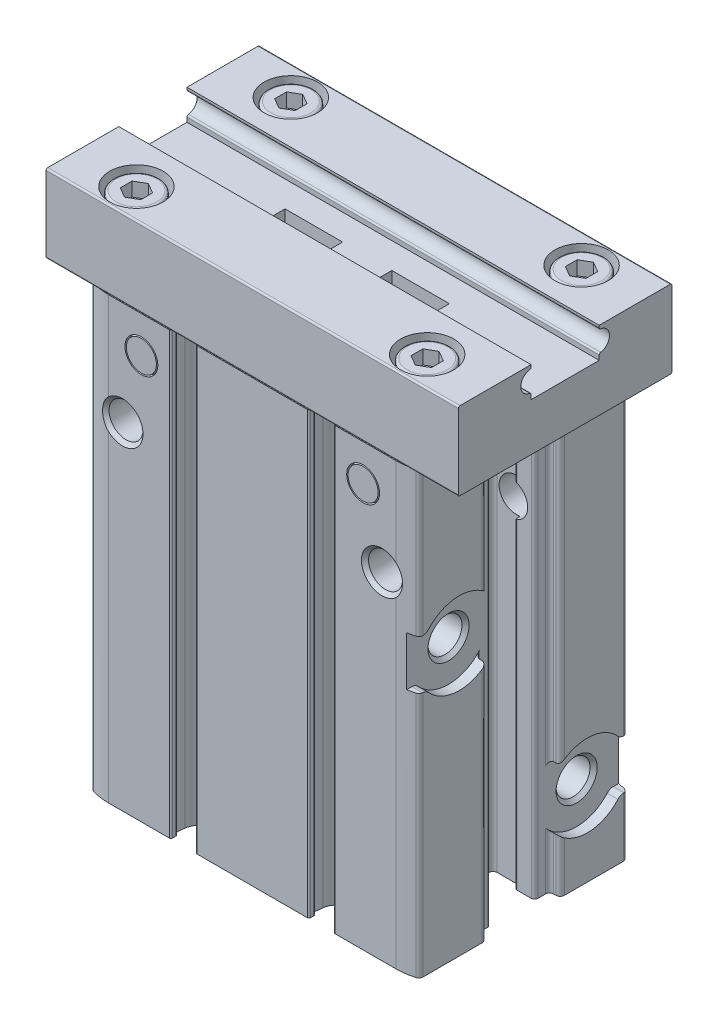
SolidWorks part; units mm, degrees
ref_plane "Front Plane" through (0, 0, 0) normal (0, 0, 1) x (1, 0, 0)
ref_plane "Top Plane" through (0, 0, 0) normal (0, 1, 0) x (1, 0, 0)
ref_plane "Right Plane" through (0, 0, 0) normal (1, 0, 0) x (0, 0, -1)
sketch "Sketch1" plane through (0, 0, 0) normal (0, 1, 0) x (1, 0, 0)
  line L0 (-17.5, -13) -> (17.5, -13)
  line L1 (20, -12.2082) -> (20, 12.2082)
  line L2 (17.5, 13) -> (-17.5, 13)
  line L3 (-20, 12.2082) -> (-20, -12.2082)
  arc A0 (-20, -12.2082) -> (-19.6429, -12.6874) centre (-19.5, -12.2082) ccw
  arc A1 (-19.6429, -12.6874) -> (-17.5, -13) centre (-17.5, -5.5) ccw
  arc A2 (17.5, -13) -> (19.6429, -12.6874) centre (17.5, -5.5) ccw
  arc A3 (19.6429, -12.6874) -> (20, -12.2082) centre (19.5, -12.2082) ccw
  arc A4 (20, 12.2082) -> (19.6429, 12.6874) centre (19.5, 12.2082) ccw
  arc A5 (19.6429, 12.6874) -> (17.5, 13) centre (17.5, 5.5) ccw
  arc A6 (-17.5, 13) -> (-19.6429, 12.6874) centre (-17.5, 5.5) ccw
  arc A7 (-19.6429, 12.6874) -> (-20, 12.2082) centre (-19.5, 12.2082) ccw
extrude "Boss-Extrude1" add sketch "Sketch1" along normal blind 53.6
ref_plane "Plane1" through (0, 41, 0) normal (0, 1, 0) x (1, 0, 0)
sketch "Sketch2" plane through (0, 41, 0) normal (0, 1, 0) x (1, 0, 0)
  line L0 (15.8, -2.6) -> (17.867, -2.6)
  line L1 (17.867, -2.6) -> (17.867, -12.567)
  line L2 (17.867, -12.567) -> (18.3, -13)
  line L3 (18.3, -13) -> (15.8, -13)
  line L4 (15.8, -13) -> (15.8, -2.6)
  line L5 (15.8, -13) -> (15.8, -2.6) construction
revolve "Cut-Revolve1" cut sketch "Sketch2" angle 360 about L5 reverse direction yes
cosmetic thread "Cosmetic Thread1" parameters "D1"=10.4, "D2"=5
sketch "Sketch3" plane through (0, 41, 0) normal (0, 1, 0) x (1, 0, 0)
  line L0 (-15.8, -2.6) -> (-13.733, -2.6)
  line L1 (-13.733, -2.6) -> (-13.733, -12.567)
  line L2 (-13.733, -12.567) -> (-13.3, -13)
  line L3 (-13.3, -13) -> (-15.8, -13)
  line L4 (-15.8, -13) -> (-15.8, -2.6)
  line L5 (-15.8, -13) -> (-15.8, -2.6) construction
revolve "Cut-Revolve2" cut sketch "Sketch3" angle 360 about L5 reverse direction yes
cosmetic thread "Cosmetic Thread2" parameters "D1"=10.4, "D2"=5
hole_wizard "Hole1" positions "Sketch5" profile "Sketch4" legacy
sketch "Sketch5" plane through (0, 0, -13) normal (0, 0, -1) x (-1, 0, 0)
  point P0 (-15.8, 41)
sketch "Sketch4" plane through (15.8, 41, -13) normal (1, 0, 0) x (0, 1, 0)
  line L0 (0, 0) -> (0, 10.4)
  line L1 (0, 10.4) -> (2.067, 10.4)
  line L2 (2.067, 10.4) -> (2.067, 0.433)
  line L3 (2.067, 0.433) -> (2.5, 0)
  line L4 (2.5, 0) -> (0, 0)
  line L5 (0, -6.4453) -> (0, 115.525) construction
  line L6 (-2.067, 0.433) -> (-2.5, 0) construction
  dimension "Diameter" = 4.134
  dimension "Depth" = 10.4
  dimension "C-Sink Angle" = 90
  dimension "C-Sink Diameter" = 5
cosmetic thread "Cosmetic Thread3" parameters "D1"=10.4, "D2"=5
sketch "Sketch6" plane through (0, 41, 0) normal (0, 1, 0) x (1, 0, 0)
  line L0 (-15.8, 13) -> (-13.3, 13)
  line L1 (-13.3, 13) -> (-13.733, 12.567)
  line L2 (-13.733, 12.567) -> (-13.733, 2.6)
  line L3 (-13.733, 2.6) -> (-15.8, 2.6)
  line L4 (-15.8, 2.6) -> (-15.8, 13)
  line L5 (-15.8, 2.6) -> (-15.8, 13) construction
revolve "Cut-Revolve3" cut sketch "Sketch6" angle 360 about L5 reverse direction yes
cosmetic thread "Cosmetic Thread4" parameters "D1"=10.4, "D2"=5
ref_plane "Plane2" through (20, 0, 0) normal (1, 0, 0) x (0, 0, -1)
sketch "Sketch7" plane through (20, 0, 0) normal (1, 0, 0) x (0, 0, -1)
  line L0 (12.2721, 7.2) -> (14, 7.2)
  line L1 (14, 7.2) -> (14, 13.2)
  line L2 (14, 13.2) -> (12.2721, 13.2)
  arc A0 (11.5268, 13.5333) -> (11.5268, 6.8667) centre (7.8, 10.2) ccw
  arc A1 (11.5268, 6.8667) -> (12.2721, 7.2) centre (12.2721, 6.2) cw
  arc A2 (12.2721, 13.2) -> (11.5268, 13.5333) centre (12.2721, 14.2) cw
extrude "Cut-Extrude1" cut sketch "Sketch7" against normal blind 1.3
sketch "Sketch8" plane through (20, 0, 0) normal (1, 0, 0) x (0, 0, -1)
  line L0 (-14, 30) -> (-12.2721, 30)
  line L1 (-12.2721, 36) -> (-14, 36)
  line L2 (-14, 36) -> (-14, 30)
  arc A0 (-12.2721, 30) -> (-11.5268, 29.6667) centre (-12.2721, 29) cw
  arc A1 (-11.5268, 29.6667) -> (-11.5268, 36.3333) centre (-7.8, 33) ccw
  arc A2 (-11.5268, 36.3333) -> (-12.2721, 36) centre (-12.2721, 37) cw
extrude "Cut-Extrude2" cut sketch "Sketch8" against normal blind 1.3
ref_plane "Plane3" through (0, 0, -7.8) normal (0, 0, 1) x (1, 0, 0)
sketch "Sketch9" plane through (0, 0, -7.8) normal (0, 0, 1) x (1, 0, 0)
  line L0 (12.7, 10.2) -> (12.7, 12.267)
  line L1 (12.7, 12.267) -> (18.267, 12.267)
  line L2 (18.267, 12.267) -> (18.7, 12.7)
  line L3 (18.7, 12.7) -> (18.7, 10.2)
  line L4 (18.7, 10.2) -> (12.7, 10.2)
  line L5 (18.7, 10.2) -> (12.7, 10.2) construction
revolve "Cut-Revolve4" cut sketch "Sketch9" angle 360 about L5 reverse direction yes
cosmetic thread "Cosmetic Thread5" parameters "D1"=6, "D2"=5
ref_plane "Plane4" through (0, 0, 7.8) normal (0, 0, 1) x (1, 0, 0)
sketch "Sketch10" plane through (0, 0, 7.8) normal (0, 0, 1) x (1, 0, 0)
  line L0 (12.7, 33) -> (12.7, 35.067)
  line L1 (12.7, 35.067) -> (18.267, 35.067)
  line L2 (18.267, 35.067) -> (18.7, 35.5)
  line L3 (18.7, 35.5) -> (18.7, 33)
  line L4 (18.7, 33) -> (12.7, 33)
  line L5 (18.7, 33) -> (12.7, 33) construction
revolve "Cut-Revolve5" cut sketch "Sketch10" angle 360 about L5 reverse direction yes
cosmetic thread "Cosmetic Thread6" parameters "D1"=6, "D2"=5
ref_plane "Plane5" through (0, 33, 0) normal (0, 1, 0) x (1, 0, 0)
sketch "Sketch11" plane through (0, 33, 0) normal (0, 1, 0) x (1, 0, 0)
  line L0 (-20, 7) -> (-20, 11.2)
  line L1 (-19.8, 11) -> (-18.7, 11)
  line L2 (-18.7, 11) -> (-18.7, 7)
  line L3 (-18.7, 7) -> (-20, 7)
  line L4 (-18.7, 7) -> (-20, 7) construction
  arc A0 (-20, 11.2) -> (-19.8, 11) centre (-19.8, 11.2) ccw
revolve "Cut-Revolve6" cut sketch "Sketch11" angle 360 about L4 reverse direction yes
sketch "Sketch12" plane through (0, 33, 0) normal (0, 1, 0) x (1, 0, 0)
  line L0 (-20, -7) -> (-20, -2.8)
  line L1 (-19.8, -3) -> (-18.7, -3)
  line L2 (-18.7, -3) -> (-18.7, -7)
  line L3 (-18.7, -7) -> (-20, -7)
  line L4 (-18.7, -7) -> (-20, -7) construction
  arc A0 (-20, -2.8) -> (-19.8, -3) centre (-19.8, -2.8) ccw
revolve "Cut-Revolve7" cut sketch "Sketch12" angle 360 about L4 reverse direction yes
sketch "Sketch13" plane through (0, 33, 0) normal (0, 1, 0) x (1, 0, 0)
  line L0 (-18.7, 7) -> (-18.7, 9.5)
  line L1 (-18.7, 9.5) -> (-18.267, 9.067)
  line L2 (-18.267, 9.067) -> (-10.7, 9.067)
  line L3 (-10.7, 9.067) -> (-10.7, 7)
  line L4 (-10.7, 7) -> (-18.7, 7)
  line L5 (-10.7, 7) -> (-18.7, 7) construction
revolve "Cut-Revolve8" cut sketch "Sketch13" angle 360 about L5 reverse direction yes
cosmetic thread "Cosmetic Thread7" parameters "D1"=8, "D2"=5
sketch "Sketch14" plane through (0, 33, 0) normal (0, 1, 0) x (1, 0, 0)
  line L0 (-18.7, -7) -> (-18.7, -4.5)
  line L1 (-18.7, -4.5) -> (-18.267, -4.933)
  line L2 (-18.267, -4.933) -> (-10.7, -4.933)
  line L3 (-10.7, -4.933) -> (-10.7, -7)
  line L4 (-10.7, -7) -> (-18.7, -7)
  line L5 (-10.7, -7) -> (-18.7, -7) construction
revolve "Cut-Revolve9" cut sketch "Sketch14" angle 360 about L5 reverse direction yes
cosmetic thread "Cosmetic Thread8" parameters "D1"=8, "D2"=5
ref_plane "Plane6" through (0, 23, 0) normal (0, 1, 0) x (1, 0, 0)
sketch "Sketch15" plane through (0, 23, 0) normal (0, 1, 0) x (1, 0, 0)
  line L0 (-20, 8) -> (-20, 10.2)
  line L1 (-20, 10.2) -> (-19.8, 10)
  line L2 (-19.8, 10) -> (-16, 10)
  line L3 (-16, 10) -> (-16, 8)
  line L4 (-16, 8) -> (-20, 8)
  line L5 (-16, 8) -> (-20, 8) construction
revolve "Cut-Revolve10" cut sketch "Sketch15" angle 360 about L5 reverse direction yes
sketch "Sketch16" plane through (0, 23, 0) normal (0, 1, 0) x (1, 0, 0)
  line L0 (-20, -8) -> (-20, -5.8)
  line L1 (-20, -5.8) -> (-19.8, -6)
  line L2 (-19.8, -6) -> (-16, -6)
  line L3 (-16, -6) -> (-16, -8)
  line L4 (-16, -8) -> (-20, -8)
  line L5 (-16, -8) -> (-20, -8) construction
revolve "Cut-Revolve11" cut sketch "Sketch16" angle 360 about L5 reverse direction yes
sketch "Sketch17" plane through (0, 0, 0) normal (0, 1, 0) x (1, 0, 0)
  line L0 (-19.5, -4.5) -> (-19.2, -4.5)
  line L1 (-18.7, -4) -> (-18.7, -3.075)
  line L2 (-18.3, -2.675) -> (-16.55, -2.675)
  line L3 (-16.35, -2.875) -> (-16.35, -3.125)
  line L4 (-16.15, -3.325) -> (-13.5, -3.325)
  line L5 (-13, -2.825) -> (-13, 2.825)
  line L6 (-13.5, 3.325) -> (-16.15, 3.325)
  line L7 (-16.35, 3.125) -> (-16.35, 2.875)
  line L8 (-16.55, 2.675) -> (-18.3, 2.675)
  line L9 (-18.7, 3.075) -> (-18.7, 4)
  line L10 (-19.2, 4.5) -> (-19.5, 4.5)
  line L11 (-20, 5) -> (-20, -5)
  arc A0 (-20, -5) -> (-19.5, -4.5) centre (-19.5, -5) cw
  arc A1 (-19.2, -4.5) -> (-18.7, -4) centre (-19.2, -4) ccw
  arc A2 (-18.7, -3.075) -> (-18.3, -2.675) centre (-18.3, -3.075) cw
  arc A3 (-16.55, -2.675) -> (-16.35, -2.875) centre (-16.55, -2.875) cw
  arc A4 (-16.35, -3.125) -> (-16.15, -3.325) centre (-16.15, -3.125) ccw
  arc A5 (-13.5, -3.325) -> (-13, -2.825) centre (-13.5, -2.825) ccw
  arc A6 (-13, 2.825) -> (-13.5, 3.325) centre (-13.5, 2.825) ccw
  arc A7 (-16.15, 3.325) -> (-16.35, 3.125) centre (-16.15, 3.125) ccw
  arc A8 (-16.35, 2.875) -> (-16.55, 2.675) centre (-16.55, 2.875) cw
  arc A9 (-18.3, 2.675) -> (-18.7, 3.075) centre (-18.3, 3.075) cw
  arc A10 (-18.7, 4) -> (-19.2, 4.5) centre (-19.2, 4) ccw
  arc A11 (-19.5, 4.5) -> (-20, 5) centre (-19.5, 5) cw
extrude "Cut-Extrude3" cut sketch "Sketch17" along normal blind 53.6
sketch "Sketch18" plane through (0, 0, 0) normal (0, 1, 0) x (1, 0, 0)
  line L0 (13, 2.825) -> (13, -2.825)
  line L1 (13.5, -3.325) -> (16.15, -3.325)
  line L2 (16.35, -3.125) -> (16.35, -2.875)
  line L3 (16.55, -2.675) -> (18.3, -2.675)
  line L4 (18.7, -3.075) -> (18.7, -4)
  line L5 (19.2, -4.5) -> (19.5, -4.5)
  line L6 (20, -5) -> (20, 5)
  line L7 (19.5, 4.5) -> (19.2, 4.5)
  line L8 (18.7, 4) -> (18.7, 3.075)
  line L9 (18.3, 2.675) -> (16.55, 2.675)
  line L10 (16.35, 2.875) -> (16.35, 3.125)
  line L11 (16.15, 3.325) -> (13.5, 3.325)
  arc A0 (13, -2.825) -> (13.5, -3.325) centre (13.5, -2.825) ccw
  arc A1 (16.15, -3.325) -> (16.35, -3.125) centre (16.15, -3.125) ccw
  arc A2 (16.35, -2.875) -> (16.55, -2.675) centre (16.55, -2.875) cw
  arc A3 (18.3, -2.675) -> (18.7, -3.075) centre (18.3, -3.075) cw
  arc A4 (18.7, -4) -> (19.2, -4.5) centre (19.2, -4) ccw
  arc A5 (19.5, -4.5) -> (20, -5) centre (19.5, -5) cw
  arc A6 (20, 5) -> (19.5, 4.5) centre (19.5, 5) cw
  arc A7 (19.2, 4.5) -> (18.7, 4) centre (19.2, 4) ccw
  arc A8 (18.7, 3.075) -> (18.3, 2.675) centre (18.3, 3.075) cw
  arc A9 (16.55, 2.675) -> (16.35, 2.875) centre (16.55, 2.875) cw
  arc A10 (16.35, 3.125) -> (16.15, 3.325) centre (16.15, 3.125) ccw
  arc A11 (13.5, 3.325) -> (13, 2.825) centre (13.5, 2.825) ccw
extrude "Cut-Extrude4" cut sketch "Sketch18" along normal blind 53.6
sketch "Sketch19" plane through (0, 0, 0) normal (1, 0, 0) x (0, 0, -1)
  line L0 (-13, 62.9) -> (-13, 53.8)
  line L1 (-12.8, 53.6) -> (12.8, 53.6)
  line L2 (13, 53.8) -> (13, 62.9)
  line L3 (12.8, 63.1) -> (4.15, 63.1)
  line L4 (4.15, 63.1) -> (4.15, 62.8361)
  line L5 (4.15, 59.9639) -> (4.15, 59.4)
  line L6 (4.15, 59.4) -> (-4.15, 59.4)
  line L7 (-4.15, 59.4) -> (-4.15, 59.9639)
  line L8 (-4.15, 62.8361) -> (-4.15, 63.1)
  line L9 (-4.15, 63.1) -> (-12.8, 63.1)
  arc A0 (-13, 53.8) -> (-12.8, 53.6) centre (-12.8, 53.8) ccw
  arc A1 (12.8, 53.6) -> (13, 53.8) centre (12.8, 53.8) ccw
  arc A2 (13, 62.9) -> (12.8, 63.1) centre (12.8, 62.9) ccw
  arc A3 (4.15, 62.8361) -> (4.3224, 62.6381) centre (4.35, 62.8361) ccw
  arc A4 (4.3224, 62.6381) -> (4.3224, 60.1619) centre (4.15, 61.4) cw
  arc A5 (4.3224, 60.1619) -> (4.15, 59.9639) centre (4.35, 59.9639) ccw
  arc A6 (-4.15, 59.9639) -> (-4.3224, 60.1619) centre (-4.35, 59.9639) ccw
  arc A7 (-4.3224, 60.1619) -> (-4.3224, 62.6381) centre (-4.15, 61.4) cw
  arc A8 (-4.3224, 62.6381) -> (-4.15, 62.8361) centre (-4.35, 62.8361) ccw
  arc A9 (-12.8, 63.1) -> (-13, 62.9) centre (-12.8, 62.9) ccw
extrude "Boss-Extrude2" add sketch "Sketch19" against normal blind 25.1 and the other way blind 25.1
ref_plane "Plane7" through (0, 0, 8.3) normal (0, 0, 1) x (1, 0, 0)
sketch "Sketch20" plane through (0, 0, 8.3) normal (0, 0, 1) x (1, 0, 0)
  line L0 (15, 10) -> (17.067, 10)
  line L1 (17.067, 10) -> (17.067, 0.433)
  line L2 (17.067, 0.433) -> (17.5, 0)
  line L3 (17.5, 0) -> (15, 0)
  line L4 (15, 0) -> (15, 10)
  line L5 (15, 0) -> (15, 10) construction
revolve "Cut-Revolve12" cut sketch "Sketch20" angle 360 about L5 reverse direction yes
cosmetic thread "Cosmetic Thread9" parameters "D1"=7, "D2"=5
ref_plane "Plane8" through (0, 0, -8.3) normal (0, 0, 1) x (1, 0, 0)
sketch "Sketch21" plane through (0, 0, -8.3) normal (0, 0, 1) x (1, 0, 0)
  line L0 (-15, 10) -> (-12.933, 10)
  line L1 (-12.933, 10) -> (-12.933, 0.433)
  line L2 (-12.933, 0.433) -> (-12.5, 0)
  line L3 (-12.5, 0) -> (-15, 0)
  line L4 (-15, 0) -> (-15, 10)
  line L5 (-15, 0) -> (-15, 10) construction
revolve "Cut-Revolve13" cut sketch "Sketch21" angle 360 about L5 reverse direction yes
cosmetic thread "Cosmetic Thread10" parameters "D1"=7, "D2"=5
ref_plane "Plane9" through (0, 0, 8.3) normal (0, 0, 1) x (1, 0, 0)
ref_plane "Plane10" through (0, 0, -8.3) normal (0, 0, 1) x (1, 0, 0)
ref_plane "Plane11" through (0, 0, 8.5) normal (0, 0, 1) x (1, 0, 0)
sketch "Sketch22" plane through (0, 0, 8.5) normal (0, 0, 1) x (1, 0, 0)
  line L0 (-15.5, 4) -> (-13.5, 4)
  line L1 (-13.5, 4) -> (-13.5, 0.2)
  line L2 (-13.5, 0.2) -> (-13.3, 0)
  line L3 (-13.3, 0) -> (-15.5, 0)
  line L4 (-15.5, 0) -> (-15.5, 4)
  line L5 (-15.5, 0) -> (-15.5, 4) construction
revolve "Cut-Revolve14" cut sketch "Sketch22" angle 360 about L5 reverse direction yes
ref_plane "Plane12" through (0, 0, -8.5) normal (0, 0, 1) x (1, 0, 0)
sketch "Sketch23" plane through (0, 0, -8.5) normal (0, 0, 1) x (1, 0, 0)
  line L0 (15.5, 4) -> (17.5, 4)
  line L1 (17.5, 4) -> (17.5, 0.2)
  line L2 (17.5, 0.2) -> (17.7, 0)
  line L3 (17.7, 0) -> (15.5, 0)
  line L4 (15.5, 0) -> (15.5, 4)
  line L5 (15.5, 0) -> (15.5, 4) construction
revolve "Cut-Revolve15" cut sketch "Sketch23" angle 360 about L5 reverse direction yes
sketch "Sketch24" plane through (0, 0, 0) normal (0, 0, 1) x (1, 0, 0)
  line L0 (0, 4) -> (11, 4)
  line L1 (11, 4) -> (11, 3)
  line L2 (11, 3) -> (10.5, 3)
  line L3 (10.5, 3) -> (10.5, 0.4)
  line L4 (10.5, 0.4) -> (10.7309, 0)
  line L5 (10.7309, 0) -> (0, 0)
  line L6 (0, 0) -> (0, 4)
  line L7 (0, 0) -> (0, 4) construction
revolve "Cut-Revolve16" cut sketch "Sketch24" angle 360 about L7 reverse direction yes
ref_plane "Plane13" through (0, 3, 0) normal (0, 1, 0) x (1, 0, 0)
sketch "Sketch25" plane through (0, 3, 0) normal (0, 1, 0) x (1, 0, 0)
  line L0 (10.735, -2.4) -> (6.4164, -2.4)
  line L1 (5.2431, -4.6425) -> (6.4387, -5.7011)
  line L2 (6.4387, 5.7011) -> (5.2431, 4.6425)
  line L3 (6.4164, 2.4) -> (10.735, 2.4)
  arc A0 (10.735, 2.4) -> (10.735, -2.4) centre (0, 0) ccw
  arc A1 (6.4164, -2.4) -> (5.2431, -4.6425) centre (-0.9, 0) cw
  arc A2 (6.4387, -5.7011) -> (6.4387, 5.7011) centre (0, 0) cw
  arc A3 (5.2431, 4.6425) -> (6.4164, 2.4) centre (-0.9, 0) cw
  circle A4 centre (7.7363, 4.4) radius 1
  circle A5 centre (7.7363, -4.4) radius 1
extrude "Boss-Extrude3" add sketch "Sketch25" along normal blind 1
ref_plane "Plane14" through (0, 16, 0) normal (0, 1, 0) x (1, 0, 0)
sketch "Sketch26" plane through (0, 16, 0) normal (0, 1, 0) x (1, 0, 0)
  line L0 (14.2, 13) -> (16.4, 13)
  line L1 (16.4, 13) -> (16.2, 12.8)
  line L2 (16.2, 12.8) -> (16.2, 9)
  line L3 (16.2, 9) -> (14.2, 9)
  line L4 (14.2, 9) -> (14.2, 13)
  line L5 (14.2, 9) -> (14.2, 13) construction
revolve "Cut-Revolve17" cut sketch "Sketch26" angle 360 about L5 reverse direction yes
sketch "Sketch27" plane through (0, 16, 0) normal (0, 1, 0) x (1, 0, 0)
  line L0 (-14.2, 13) -> (-12, 13)
  line L1 (-12, 13) -> (-12.2, 12.8)
  line L2 (-12.2, 12.8) -> (-12.2, 9)
  line L3 (-12.2, 9) -> (-14.2, 9)
  line L4 (-14.2, 9) -> (-14.2, 13)
  line L5 (-14.2, 9) -> (-14.2, 13) construction
revolve "Cut-Revolve18" cut sketch "Sketch27" angle 360 about L5 reverse direction yes
sketch "Sketch28" plane through (0, 0, 0) normal (0, 1, 0) x (1, 0, 0)
  line L0 (6.513, 11.9703) -> (6.6089, 11.0109)
  line L1 (10.1911, 11.0109) -> (10.287, 11.9703)
  line L2 (9.9, 12.39) -> (9.9, 12.8)
  line L3 (10.1, 13) -> (6.7, 13)
  line L4 (6.9, 12.8) -> (6.9, 12.39)
  arc A0 (6.706, 12.1901) -> (6.513, 11.9703) centre (6.712, 11.9902) ccw
  arc A1 (6.6089, 11.0109) -> (10.1911, 11.0109) centre (8.4, 11.19) ccw
  arc A2 (10.287, 11.9703) -> (10.094, 12.1901) centre (10.088, 11.9902) ccw
  arc A3 (10.094, 12.1901) -> (9.9, 12.39) centre (10.1, 12.39) cw
  arc A4 (9.9, 12.8) -> (10.1, 13) centre (10.1, 12.8) cw
  arc A5 (6.7, 13) -> (6.9, 12.8) centre (6.7, 12.8) cw
  arc A6 (6.9, 12.39) -> (6.706, 12.1901) centre (6.7, 12.39) cw
extrude "Cut-Extrude5" cut sketch "Sketch28" along normal blind 53.6
sketch "Sketch29" plane through (0, 0, 0) normal (0, 1, 0) x (1, 0, 0)
  line L0 (-10.288, 11.9802) -> (-10.1911, 11.0109)
  line L1 (-6.6089, 11.0109) -> (-6.512, 11.9802)
  line L2 (-6.9, 12.4) -> (-6.9, 12.8)
  line L3 (-6.7, 13) -> (-10.1, 13)
  line L4 (-9.9, 12.8) -> (-9.9, 12.4)
  arc A0 (-10.0945, 12.2001) -> (-10.288, 11.9802) centre (-10.089, 12.0002) ccw
  arc A1 (-10.1911, 11.0109) -> (-6.6089, 11.0109) centre (-8.4, 11.19) ccw
  arc A2 (-6.512, 11.9802) -> (-6.7055, 12.2001) centre (-6.711, 12.0002) ccw
  arc A3 (-6.7055, 12.2001) -> (-6.9, 12.4) centre (-6.7, 12.4) cw
  arc A4 (-6.9, 12.8) -> (-6.7, 13) centre (-6.7, 12.8) cw
  arc A5 (-10.1, 13) -> (-9.9, 12.8) centre (-10.1, 12.8) cw
  arc A6 (-9.9, 12.4) -> (-10.0945, 12.2001) centre (-10.1, 12.4) cw
extrude "Cut-Extrude6" cut sketch "Sketch29" along normal blind 53.6
sketch "Sketch30" plane through (0, 0, 0) normal (0, 1, 0) x (1, 0, 0)
  line L0 (6.9, -12.4) -> (6.9, -12.8)
  line L1 (6.7, -13) -> (10.1, -13)
  line L2 (9.9, -12.8) -> (9.9, -12.4)
  line L3 (10.288, -11.9802) -> (10.1911, -11.0109)
  line L4 (6.6089, -11.0109) -> (6.512, -11.9802)
  arc A0 (6.512, -11.9802) -> (6.7055, -12.2001) centre (6.711, -12.0002) ccw
  arc A1 (6.7055, -12.2001) -> (6.9, -12.4) centre (6.7, -12.4) cw
  arc A2 (6.9, -12.8) -> (6.7, -13) centre (6.7, -12.8) cw
  arc A3 (10.1, -13) -> (9.9, -12.8) centre (10.1, -12.8) cw
  arc A4 (9.9, -12.4) -> (10.0945, -12.2001) centre (10.1, -12.4) cw
  arc A5 (10.0945, -12.2001) -> (10.288, -11.9802) centre (10.089, -12.0002) ccw
  arc A6 (10.1911, -11.0109) -> (6.6089, -11.0109) centre (8.4, -11.19) ccw
extrude "Cut-Extrude7" cut sketch "Sketch30" along normal blind 53.6
sketch "Sketch31" plane through (0, 0, 0) normal (0, 1, 0) x (1, 0, 0)
  line L0 (-9.9, -12.4) -> (-9.9, -12.8)
  line L1 (-10.1, -13) -> (-6.7, -13)
  line L2 (-6.9, -12.8) -> (-6.9, -12.4)
  line L3 (-6.512, -11.9802) -> (-6.6089, -11.0109)
  line L4 (-10.1911, -11.0109) -> (-10.288, -11.9802)
  arc A0 (-10.288, -11.9802) -> (-10.0945, -12.2001) centre (-10.089, -12.0002) ccw
  arc A1 (-10.0945, -12.2001) -> (-9.9, -12.4) centre (-10.1, -12.4) cw
  arc A2 (-9.9, -12.8) -> (-10.1, -13) centre (-10.1, -12.8) cw
  arc A3 (-6.7, -13) -> (-6.9, -12.8) centre (-6.7, -12.8) cw
  arc A4 (-6.9, -12.4) -> (-6.7055, -12.2001) centre (-6.7, -12.4) cw
  arc A5 (-6.7055, -12.2001) -> (-6.512, -11.9802) centre (-6.711, -12.0002) ccw
  arc A6 (-6.6089, -11.0109) -> (-10.1911, -11.0109) centre (-8.4, -11.19) ccw
extrude "Cut-Extrude8" cut sketch "Sketch31" along normal blind 53.6
ref_plane "Plane15" through (0, 49.16, 0) normal (0, 1, 0) x (1, 0, 0)
sketch "Sketch32" plane through (0, 49.16, 0) normal (0, 1, 0) x (1, 0, 0)
  line L0 (13.5, 13) -> (15.5, 13)
  line L1 (15.5, 13) -> (15.5, -13)
  line L2 (15.5, -13) -> (13.5, -13)
  line L3 (13.5, -13) -> (13.5, 13)
  line L4 (13.5, -13) -> (13.5, 13) construction
revolve "Cut-Revolve19" cut sketch "Sketch32" angle 360 about L4 reverse direction yes
sketch "Sketch33" plane through (0, 49.16, 0) normal (0, 1, 0) x (1, 0, 0)
  line L0 (-13.5, 13) -> (-11.5, 13)
  line L1 (-11.5, 13) -> (-11.5, -13)
  line L2 (-11.5, -13) -> (-13.5, -13)
  line L3 (-13.5, -13) -> (-13.5, 13)
  line L4 (-13.5, -13) -> (-13.5, 13) construction
revolve "Cut-Revolve20" cut sketch "Sketch33" angle 360 about L4 reverse direction yes
sketch "Sketch34" plane through (0, 49.16, 0) normal (0, 1, 0) x (1, 0, 0)
  line L0 (13.5, 13) -> (15.3312, 13)
  line L1 (15.3312, 13) -> (15.5, 12.37)
  line L2 (15.5, 12.37) -> (15.5, -12.37)
  line L3 (15.5, -12.37) -> (15.3312, -13)
  line L4 (15.3312, -13) -> (13.5, -13)
  line L5 (13.5, -13) -> (13.5, 13)
  line L6 (13.5, -13) -> (13.5, 13) construction
revolve "Revolve1" add sketch "Sketch34" angle 360 about L6 reverse direction yes
sketch "Sketch35" plane through (0, 49.16, 0) normal (0, 1, 0) x (1, 0, 0)
  line L0 (-13.5, 13) -> (-11.6688, 13)
  line L1 (-11.6688, 13) -> (-11.5, 12.37)
  line L2 (-11.5, 12.37) -> (-11.5, -12.37)
  line L3 (-11.5, -12.37) -> (-11.6688, -13)
  line L4 (-11.6688, -13) -> (-13.5, -13)
  line L5 (-13.5, -13) -> (-13.5, 13)
  line L6 (-13.5, -13) -> (-13.5, 13) construction
revolve "Revolve2" add sketch "Sketch35" angle 360 about L6 reverse direction yes
ref_plane "Plane16" through (0, 0, 0) normal (0, 1, 0) x (1, 0, 0)
ref_plane "Plane17" through (0, 0, -8.3) normal (0, 0, 1) x (1, 0, 0)
ref_plane "Plane18" through (0, 0, 8.3) normal (0, 0, 1) x (1, 0, 0)
sketch "Sketch36" plane through (0, 0, 0) normal (0, 0, 1) x (1, 0, 0)
  line L0 (3, 57.4) -> (10, 57.4)
  line L1 (10, 57.4) -> (10, 59.4)
  line L2 (10, 59.4) -> (3, 59.4)
  line L3 (3, 59.4) -> (3, 57.4)
extrude "Cut-Extrude9" cut sketch "Sketch36" along normal blind 1 and the other way blind 1
sketch "Sketch37" plane through (0, 0, 0) normal (0, 0, 1) x (1, 0, 0)
  line L0 (-10, 57.4) -> (-3, 57.4)
  line L1 (-3, 57.4) -> (-3, 59.4)
  line L2 (-3, 59.4) -> (-10, 59.4)
  line L3 (-10, 59.4) -> (-10, 57.4)
extrude "Cut-Extrude10" cut sketch "Sketch37" along normal blind 1 and the other way blind 1
ref_plane "Plane19" through (0, 0, 9.4) normal (0, 0, 1) x (1, 0, 0)
sketch "Sketch38" plane through (0, 0, 9.4) normal (0, 0, 1) x (1, 0, 0)
  line L0 (17.7, 63.1) -> (20.95, 63.1)
  line L1 (20.95, 63.1) -> (20.95, 59.7)
  line L2 (20.95, 59.7) -> (20.45, 59.7)
  line L3 (20.45, 59.7) -> (20.45, 62.4)
  line L4 (20.15, 62.7) -> (17.7, 62.7)
  line L5 (17.7, 62.7) -> (17.7, 63.1)
  line L6 (17.7, 59.7) -> (17.7, 63.1) construction
  arc A0 (20.45, 62.4) -> (20.15, 62.7) centre (20.15, 62.4) ccw
revolve "Cut-Revolve21" cut sketch "Sketch38" angle 360 about L6 reverse direction yes
sketch "Sketch39" plane through (0, 0, 9.4) normal (0, 0, 1) x (1, 0, 0)
  line L0 (-17.7, 63.1) -> (-14.45, 63.1)
  line L1 (-14.45, 63.1) -> (-14.45, 59.7)
  line L2 (-14.45, 59.7) -> (-14.95, 59.7)
  line L3 (-14.95, 59.7) -> (-14.95, 62.4)
  line L4 (-15.25, 62.7) -> (-17.7, 62.7)
  line L5 (-17.7, 62.7) -> (-17.7, 63.1)
  line L6 (-17.7, 59.7) -> (-17.7, 63.1) construction
  arc A0 (-14.95, 62.4) -> (-15.25, 62.7) centre (-15.25, 62.4) ccw
revolve "Cut-Revolve22" cut sketch "Sketch39" angle 360 about L6 reverse direction yes
ref_plane "Plane20" through (0, 0, -9.4) normal (0, 0, 1) x (1, 0, 0)
sketch "Sketch40" plane through (0, 0, -9.4) normal (0, 0, 1) x (1, 0, 0)
  line L0 (17.7, 63.1) -> (20.95, 63.1)
  line L1 (20.95, 63.1) -> (20.95, 59.7)
  line L2 (20.95, 59.7) -> (20.45, 59.7)
  line L3 (20.45, 59.7) -> (20.45, 62.4)
  line L4 (20.15, 62.7) -> (17.7, 62.7)
  line L5 (17.7, 62.7) -> (17.7, 63.1)
  line L6 (17.7, 59.7) -> (17.7, 63.1) construction
  arc A0 (20.45, 62.4) -> (20.15, 62.7) centre (20.15, 62.4) ccw
revolve "Cut-Revolve23" cut sketch "Sketch40" angle 360 about L6 reverse direction yes
sketch "Sketch41" plane through (0, 0, -9.4) normal (0, 0, 1) x (1, 0, 0)
  line L0 (-17.7, 63.1) -> (-14.45, 63.1)
  line L1 (-14.45, 63.1) -> (-14.45, 59.7)
  line L2 (-14.45, 59.7) -> (-14.95, 59.7)
  line L3 (-14.95, 59.7) -> (-14.95, 62.4)
  line L4 (-15.25, 62.7) -> (-17.7, 62.7)
  line L5 (-17.7, 62.7) -> (-17.7, 63.1)
  line L6 (-17.7, 59.7) -> (-17.7, 63.1) construction
  arc A0 (-14.95, 62.4) -> (-15.25, 62.7) centre (-15.25, 62.4) ccw
revolve "Cut-Revolve24" cut sketch "Sketch41" angle 360 about L6 reverse direction yes
ref_plane "Plane21" through (0, 62.7, 0) normal (0, 1, 0) x (1, 0, 0)
sketch "Sketch42" plane through (0, 62.7, 0) normal (0, 1, 0) x (1, 0, 0)
  line L0 (16.45, -10.1217) -> (17.7, -10.8434)
  line L1 (17.7, -10.8434) -> (18.95, -10.1217)
  line L2 (18.95, -10.1217) -> (18.95, -8.6783)
  line L3 (18.95, -8.6783) -> (17.7, -7.9566)
  line L4 (17.7, -7.9566) -> (16.45, -8.6783)
  line L5 (16.45, -8.6783) -> (16.45, -10.1217)
extrude "Cut-Extrude11" cut sketch "Sketch42" against normal blind 1.7
sketch "Sketch43" plane through (0, 62.7, 0) normal (0, 1, 0) x (1, 0, 0)
  line L0 (17.7, -9.4) -> (17.7, 9.4)
  line L1 (17.7, -9.4) -> (-17.7, -9.4)
pattern_linear "LPattern1" count 2 spacing 18.8 along (0, 0, -1) count 2 spacing 35.4 along (-1, 0, 0) of "Cut-Extrude11"
ref_plane "Plane22" through (3, 0, 0) normal (1, 0, 0) x (0, 0, -1)
ref_plane "Plane23" through (-3, 0, 0) normal (1, 0, 0) x (0, 0, -1)
ref_plane "Plane24" through (-20, 0, 0) normal (1, 0, 0) x (0, 0, -1)
ref_plane "Plane25" through (18.7, 0, 0) normal (1, 0, 0) x (0, 0, -1)
ref_plane "Plane26" through (0, 0, 0) normal (0, 1, 0) x (1, 0, 0)
ref_plane "Plane27" through (0, 63.1, 0) normal (0, 1, 0) x (1, 0, 0)
ref_plane "ANBAU XY" through (0, 0, 0) normal (0, -1, 0) x (-1, 0, 0)
ref_plane "ANBAU XZ" through (0, 0, 0) normal (-1, 0, 0) x (0, 0, 1)
ref_plane "ANBAU YZ" through (0, 0, 0) normal (0, 0, -1) x (-1, 0, 0)
ref_axis "ANBAU X" through (0, 0, 50) along (0, 0, -1)
ref_axis "ANBAU Y" through (-80.9, 0, 0) along (1, 0, 0)
ref_axis "ANBAU Z" through (0, -50, 0) along (0, 1, 0)
sketch3d "ANBAU"
  point P0 (0, 0, 0)
ref_plane "CP1 XY" through (0, 63.1, 0) normal (0, -1, 0) x (-1, 0, 0)
ref_plane "CP1 XZ" through (0, 0, 0) normal (0, 0, -1) x (-1, 0, 0)
ref_plane "CP1 YZ" through (0, 0, 0) normal (1, 0, 0) x (0, 0, -1)
ref_axis "CP1 X" through (-80.9, 63.1, 0) along (1, 0, 0)
ref_axis "CP1 Y" through (0, 63.1, -50) along (0, 0, 1)
ref_axis "CP1 Z" through (0, -50, 0) along (0, 1, 0)
sketch3d "CP1"
  point P0 (0, 63.1, 0)
ref_plane "DROSSEL_S XY" through (18.7, 0, 0) normal (1, 0, 0) x (0, 0, -1)
ref_plane "DROSSEL_S XZ" through (0, 33, 0) normal (0, -1, 0) x (-1, 0, 0)
ref_plane "DROSSEL_S YZ" through (0, 0, 7.8) normal (0, 0, -1) x (-1, 0, 0)
ref_axis "DROSSEL_S X" through (18.7, 33, 80.9) along (0, 0, -1)
ref_axis "DROSSEL_S Y" through (18.7, -50, 7.8) along (0, 1, 0)
ref_axis "DROSSEL_S Z" through (80.9, 33, 7.8) along (-1, 0, 0)
sketch3d "DROSSEL_S"
  point P0 (18.7, 33, 7.8)
ref_plane "GRIFF 1 XY" through (3, 0, 0) normal (1, 0, 0) x (0, 0, -1)
ref_plane "GRIFF 1 XZ" through (0, 59.4, 0) normal (0, -1, 0) x (-1, 0, 0)
ref_plane "GRIFF 1 YZ" through (0, 0, 0) normal (0, 0, -1) x (-1, 0, 0)
ref_axis "GRIFF 1 X" through (3, 59.4, 80.9) along (0, 0, -1)
ref_axis "GRIFF 1 Y" through (3, -50, 0) along (0, 1, 0)
ref_axis "GRIFF 1 Z" through (80.9, 59.4, 0) along (-1, 0, 0)
sketch3d "GRIFF 1"
  point P0 (3, 59.4, 0)
ref_plane "GRIFF 2 XY" through (-3, 0, 0) normal (-1, 0, 0) x (0, 0, 1)
ref_plane "GRIFF 2 XZ" through (0, 59.4, 0) normal (0, -1, 0) x (-1, 0, 0)
ref_plane "GRIFF 2 YZ" through (0, 0, 0) normal (0, 0, 1) x (1, 0, 0)
ref_axis "GRIFF 2 X" through (-3, 59.4, -80.9) along (0, 0, 1)
ref_axis "GRIFF 2 Y" through (-3, -50, 0) along (0, 1, 0)
ref_axis "GRIFF 2 Z" through (-80.9, 59.4, 0) along (1, 0, 0)
sketch3d "GRIFF 2"
  point P0 (-3, 59.4, 0)
other "Freeze***"
